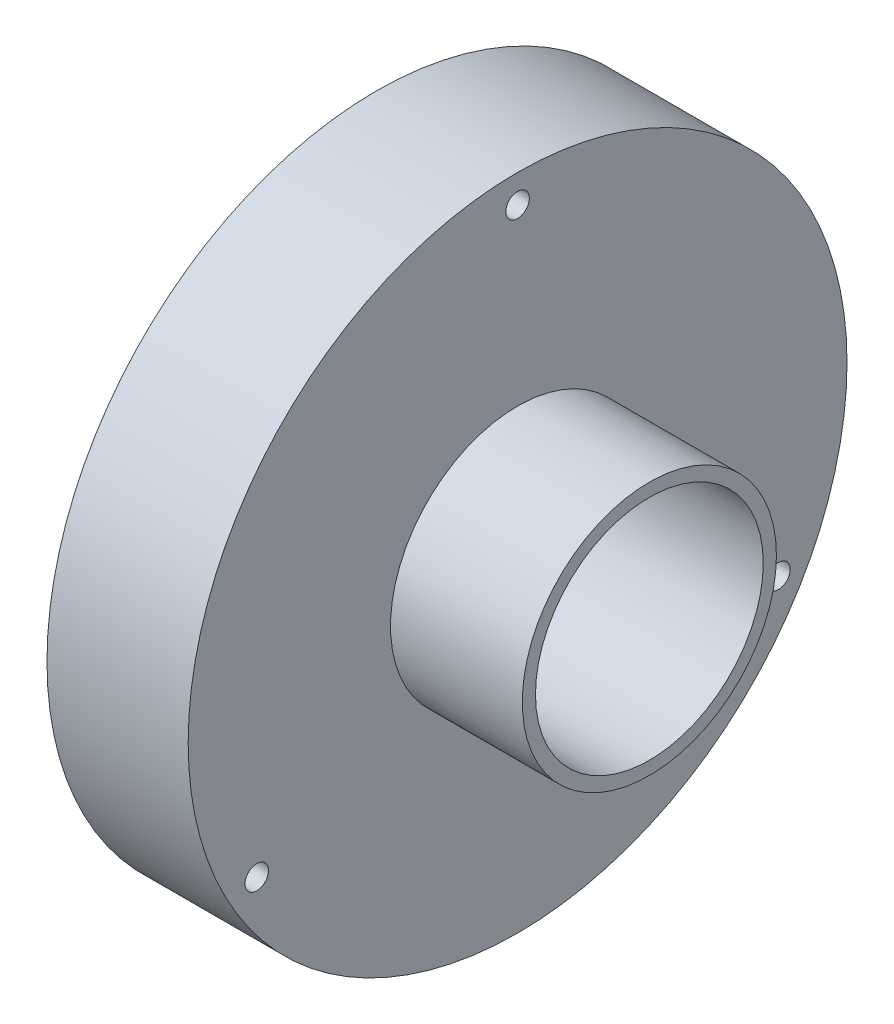
SolidWorks part; units mm, degrees
ref_plane "Plane1" through (0, 0, 0) normal (0, 0, 1) x (1, 0, 0)
ref_plane "Plane2" through (0, 0, 0) normal (0, 1, 0) x (1, 0, 0)
ref_plane "Plane3" through (0, 0, 0) normal (1, 0, 0) x (0, 0, -1)
sketch "HoldingSke" plane through (0, 0, 0) normal (0, 1, 0) x (1, 0, 0)
  line L0 (0, 0) -> (1.1472, -1.6383)
  line L1 (-15, 0) -> (100, 0) construction
  line L2 (0, 0) -> (-2.1039, 2.3779)
  line L3 (0, 0) -> (-11.863, 4.5341)
  line L4 (0, 0) -> (4.9534, 7.0742)
  line L5 (0, 0) -> (-23.7986, -8.8762)
  line L6 (0, 0) -> (-10.5278, -7.1032)
  line L7 (-2.1039, 2.3779) -> (3.3635, 27.1825)
  line L8 (-76.2, 2.8779) -> (-54.61, 2.8779)
  line L9 (-71.009, 38.7566) -> (-53.1078, 45.2721)
  line L10 (-76.2, 71.12) -> (104.1128, 71.12)
  line L11 (0, 0) -> (-5, 0)
  line L12 (-76.2, 101.6) -> (-76.181, 101.6)
  line L13 (24.9733, 27.94) -> (52.9518, 28.4284)
  line L14 (24.9733, 27.94) -> (24.9743, 27.94)
  line L15 (24.9733, 27.94) -> (100.4006, 29.5858)
  circle A0 centre (0, 0) radius 17.5
  circle A1 centre (0, 0) radius 12.7
  circle A2 centre (0, 0) radius 12.7
  dimension "Num_teeth" = 55
  dimension "Pitch_radius" = 180.3128
  dimension "Width" = 5
  dimension "Diameter" = 35
sketch "BasProSke" plane through (0, 0, 0) normal (0, 1, 0) x (1, 0, 0)
  line L0 (-10, 0) -> (60, 0) construction
  line L1 (0, 13.25) -> (0, 17.5)
  line L2 (0, 13.25) -> (5, 13.25)
  line L3 (5, 13.25) -> (5, 17.5)
  line L4 (5, 17.5) -> (0, 17.5)
  dimension "Thickness" = 5
  dimension "Diameter" = 35
revolve "Base-Revolve" add sketch "BasProSke" angle 360 about L0
sketch "TooCutSke" plane through (0, 0, 0) normal (1, 0, 0) x (0, 0, -1)
  line L3 (0.4401, 13.743) -> (0.4401, 53.6633) construction
  line L4 (0, 0) -> (0, 59.563) construction
  line L5 (0, 0) -> (-3.9007, 68.2161) construction
  line L6 (-5.9882, 11.3053) -> (37.1172, 13.7701) construction
  circle A0 centre (0, 0) radius 13.75 construction
  circle A1 centre (0, 0) radius 14.376 construction
  circle A2 centre (0, 0) radius 11.6287 construction
  circle A3 centre (0, 0) radius 13.2246 construction
  arc A4 (0.6177, 13.2102) -> (0.1634, 14.3751) centre (-5.9882, 11.3053) ccw
  arc A5 (0.6177, 13.2102) -> (-0.6177, 13.2102) centre (0, 0) ccw
  arc A6 (0.1634, 14.3751) -> (-0.1634, 14.3751) centre (0, 0) ccw
  arc A7 (-0.1634, 14.3751) -> (-0.6177, 13.2102) centre (5.9882, 11.3053) ccw
extrude "ToothCut" cut sketch "TooCutSke" along normal through all
fillet "Breaks" [suppressed] radius 0.05
fillet "RootFillets" [suppressed] radius 0.126
pattern_circular "TeethCuts" count 55 every 6.545 about axis through (-10, 0, 0) along (1, 0, 0) of "RootFillets", "Breaks", "ToothCut"
sketch "Sketch1" plane through (5, 0, 0) normal (1, 0, 0) x (0, 0, -1)
  circle A0 centre (0, 0) radius 17.5
  circle A1 centre (0, 0) radius 5.25
  dimension "D1" = 10.5
extrude "Boss-Extrude1" add sketch "Sketch1" along normal blind 2.5
sketch "Sketch2" plane through (5, 0, 0) normal (-1, 0, 0) x (0, 0, 1)
  circle A0 centre (0, 0) radius 5.25
  circle A1 centre (0, 0) radius 7.75
  dimension "D1" = 10.5
  dimension "D2" = 15.5
extrude "Boss-Extrude2" add sketch "Sketch2" along normal blind 2.5
sketch "Sketch3" plane through (7.5, 0, 0) normal (1, 0, 0) x (0, 0, -1)
  circle A0 centre (0, 0) radius 6.05
  dimension "D1" = 12.1
extrude "Cut-Extrude1" cut sketch "Sketch3" against normal blind 3.5
hole_wizard "M1.6 Tapped Hole1" positions "Sketch5" profile "Sketch6" tap size "M1.6" standard "ISO" end condition through all
sketch "Sketch5" plane through (7.5, 0, 0) normal (1, 0, 0) x (0, 0, -1)
  line L2 (0, 19.3966) -> (0, 0) construction
  point P0 (0, 16)
  dimension "D1" = 16
cosmetic thread "Hole Thread1" parameters "D2"=1.6
sketch "Sketch6" plane through (7.5, 16, 0) normal (0, 1, 0) x (0, 0, -1)
  line L0 (0, 0) -> (0, 7.5)
  line L1 (0, 7.5) -> (0.625, 7.5)
  line L2 (0.625, 7.5) -> (0.625, 0)
  line L5 (0.625, 0) -> (0, 0)
  line L11 (0, -6.35) -> (0, 107.95) construction
  dimension "Thru Tap Drill Dia." = 1.25
  dimension "Thru Tap Drill Depth" = 7.5
pattern_circular "CirPattern1" count 3 over 360 about axis through (7.5, 0, 0) along (-1, 0, 0) of "M1.6 Tapped Hole1"
sketch "Sketch7" plane through (7.5, 0, 0) normal (1, 0, 0) x (0, 0, -1)
  circle A0 centre (0, 0) radius 6.75
  dimension "D1" = 13.5
extrude "Boss-Extrude3" add sketch "Sketch7" along normal blind 7
sketch "Sketch8" plane through (14.5, 0, 0) normal (1, 0, 0) x (0, 0, -1)
  circle A0 centre (0, 0) radius 6.05
  dimension "D1" = 12.1
extrude "Cut-Extrude2" cut sketch "Sketch8" against normal blind 7
equation "' \"Module@HoldingSke\" = 6.35"
equation "' \"Num_teeth@HoldingSke\" = 24"
equation "' \"Ap@HoldingSke\" =  14.5"
equation "' \"Ap@HoldingSke\" = 14.5"
equation "' \"Width@HoldingSke\" = 12"
equation "' \"Diameter@HoldingSke\" = 8 * 25.4"
equation "' \"Show_teeth@HoldingSke\" = 100"
equation "' \"Backlash@HoldingSke\" = 0.009 * 25.4"
equation "' \"Addendum_fac@HoldingSke\" = 1.0"
equation "' \"Dedendum_fac@HoldingSke\" = 1.25"
equation "' \"Dedendum_add@HoldingSke\" = 0.00005 * 25.4"
equation "' \"Clearance_fac@HoldingSke\" = 0.25"
equation "\"Pitch@HoldingSke\" = 1 / \"Module@HoldingSke\" "
equation "\"Overcut_dia@TooCutSke\" = (\"Num_teeth@HoldingSke\" - 2 * \"Addendum_fac@HoldingSke\") / \"Pitch@HoldingSke\" - 0.002 * 25.4"
equation "\"Pitch_dia@TooCutSke\" = \"Num_teeth@HoldingSke\" / \"Pitch@HoldingSke\""
equation "\"Base_dia@TooCutSke\" = \"Num_teeth@HoldingSke\" / \"Pitch@HoldingSke\" * cos((\"Ap@HoldingSke\"  * 3.14159265 / 180)) * 0.90"
equation "\"Root_dia@TooCutSke\" = \"Num_teeth@HoldingSke\"  / \"Pitch@HoldingSke\" + 2 *  \"Dedendum_fac@HoldingSke\"/ \"Pitch@HoldingSke\" + \"Dedendum_add@HoldingSke\" * 2"
equation "\"Half_ang@TooCutSke\" = 180 / \"Num_teeth@HoldingSke\""
equation "\"Half_CT@TooCutSke\" = \"Num_teeth@HoldingSke\" / \"Pitch@HoldingSke\" * sin((3.14159265 / 2 / \"Num_teeth@HoldingSke\")) / 2 + 10 * \"Backlash@HoldingSke\" / 4"
equation "\"Flank_rad@TooCutSke\" = \"Num_teeth@HoldingSke\" / \"Pitch@HoldingSke\" / 4"
equation "\"Radius@RootFillets\"= \"Clearance_fac@HoldingSke\" / \"Pitch@HoldingSke\" + \"Dedendum_add@HoldingSke\""
equation "\"Break_rad@Breaks\" = 0.02 / \"Pitch@HoldingSke\" * 5"
equation "\"Num_teeth@TeethCuts\" = int( \"Show_teeth@HoldingSke\" ) + 1"
equation "\"Num_teeth@TeethCuts\" = ((sgn( \"Num_teeth@TeethCuts\" - \"Num_teeth@HoldingSke\" )-1)*( \"Num_teeth@TeethCuts\" - \"Num_teeth@HoldingSke\" ))/-2+ \"Num_teeth@HoldingSke\""
equation "\"Num_teeth@TeethCuts\" = ((sgn( \"Num_teeth@TeethCuts\" - 2.0)+1)*( \"Num_teeth@TeethCuts\" - 2.0))/2 +2.0"
equation "\"Angle@TeethCuts\" = 360.0 / \"Num_teeth@HoldingSke\""
equation "\"Diameter@BasProSke\" = \"Num_teeth@HoldingSke\"  / \"Pitch@HoldingSke\" + 2 *  \"Dedendum_fac@HoldingSke\"/ \"Pitch@HoldingSke\" + \"Dedendum_add@HoldingSke\" * 2 + 0.002 * 25.4"
equation "\"Diameter@BasProSke\" = ((sgn( \"Diameter@BasProSke\"  - \"Diameter@HoldingSke\" )+1)*( \"Diameter@BasProSke\"  - \"Diameter@HoldingSke\" ))/2 + \"Diameter@HoldingSke\""
equation "\"Inside_diameter@BasProSke\" =  (\"Num_teeth@HoldingSke\" - 2 * \"Addendum_fac@HoldingSke\") / \"Pitch@HoldingSke\" "
equation "\"Thickness@BasProSke\"  = \"Width@HoldingSke\""
